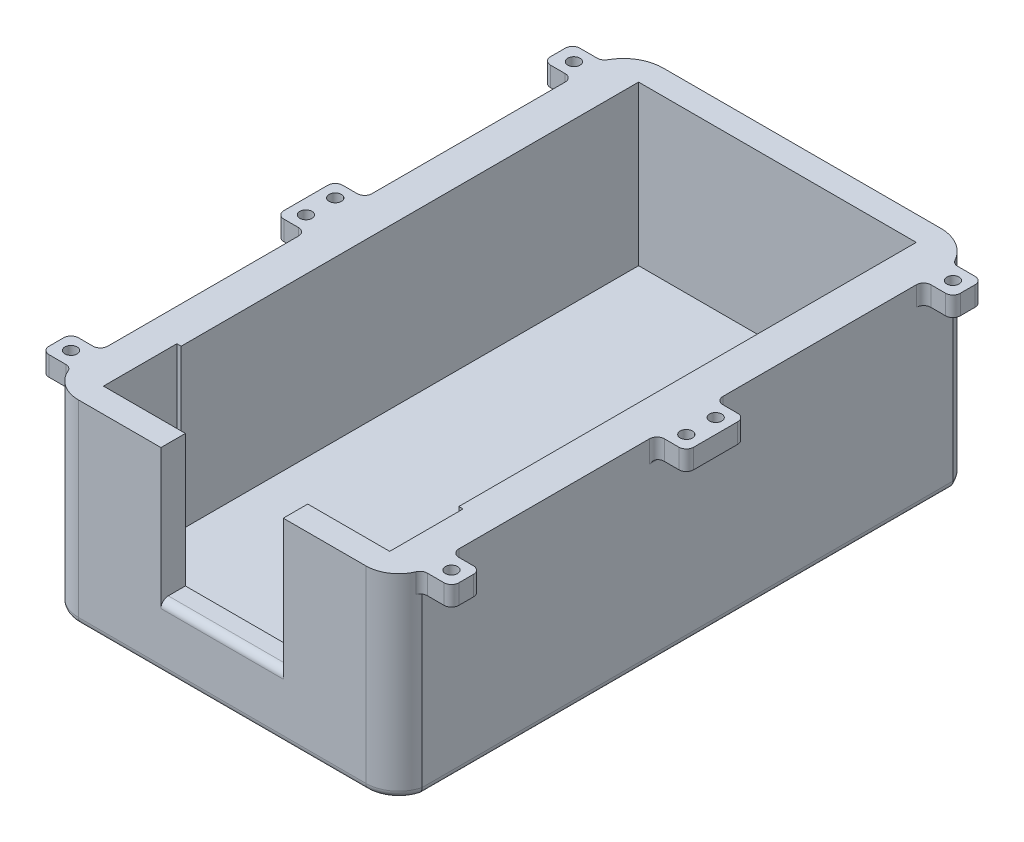
SolidWorks part; units mm, degrees
ref_plane "Front Plane" through (0, 0, 0) normal (0, 0, 1) x (1, 0, 0)
ref_plane "Top Plane" through (0, 0, 0) normal (0, 1, 0) x (1, 0, 0)
ref_plane "Right Plane" through (0, 0, 0) normal (1, 0, 0) x (0, 0, -1)
sketch "Sketch2" plane through (0, 0, 0) normal (0, 1, 0) x (1, 0, 0)
  line L0 (0, 0) -> (0, 286.8389) construction
  line L1 (0, 0) -> (357.4754, 0) construction
  line L2 (0, 0) -> (117, 0)
  line L3 (0, 0) -> (0, 30)
  line L4 (0, 30) -> (1.75, 30)
  line L5 (1.75, 30) -> (1.75, 217)
  line L6 (1.75, 217) -> (115.25, 217)
  line L7 (115.25, 217) -> (115.25, 30)
  line L8 (115.25, 30) -> (117, 30)
  line L9 (117, 30) -> (117, 0)
  line L10 (1.75, 227) -> (115.25, 227)
  line L11 (-13.25, 217) -> (-13.25, 0)
  line L12 (130.25, 217) -> (130.25, 0)
  line L13 (-13.25, 0) -> (0, 0)
  line L14 (1.75, 227) -> (1.75, 217) construction
  line L15 (-0.2607, -10) -> (117.2607, -10)
  arc A0 (1.75, 227) -> (-13.25, 217) centre (1.75, 210.75) ccw
  arc A1 (115.25, 227) -> (130.25, 217) centre (115.25, 210.75) cw
  arc A2 (117.2607, -10) -> (130.25, 0) centre (117.2607, 3.4361) ccw
  arc A3 (-0.2607, -10) -> (-13.25, 0) centre (-0.2607, 3.4361) cw
  dimension "D11" = 10
  dimension "D12" = 217
  dimension "D14" = 113.5
  dimension "D15" = 13.4361
  dimension "D16" = 13.4361
  dimension "D1" = 117
  dimension "D2" = 113.5
  dimension "D3" = 1.75
  dimension "D4" = 1.75
  dimension "D5" = 217
  dimension "D6" = 30
  dimension "D7" = 30
  dimension "D8" = 15
  dimension "D9" = 15
  dimension "D10" = 10
  dimension "D13" = 217
extrude "Boss-Extrude1" add sketch "Sketch2" along normal blind 65 contours A3 L15 A2 L12 A1 L10 A0 L11 L3 L4 L5 L6 L7 L8 L9 L2 region at (-10.4794, 0, -108.5)
sketch "Sketch3" plane through (0, 0, 0) normal (0, -1, 0) x (1, 0, 0)
  line L0 (1.75, -227) -> (115.25, -227) construction
  line L1 (130.25, -217) -> (130.25, 0) construction
  line L2 (-0.2607, 10) -> (117.2607, 10) construction
  line L3 (-13.25, -217) -> (-13.25, 0) construction
  line L4 (1.75, -227) -> (115.25, -227)
  line L5 (130.25, -217) -> (130.25, 0)
  line L6 (-0.2607, 10) -> (117.2607, 10)
  line L7 (-13.25, -217) -> (-13.25, 0)
  arc A0 (-13.25, -217) -> (1.75, -227) centre (1.75, -210.75) ccw construction
  arc A1 (115.25, -227) -> (130.25, -217) centre (115.25, -210.75) ccw construction
  arc A2 (130.25, 0) -> (117.2607, 10) centre (117.2607, -3.4361) ccw construction
  arc A3 (-0.2607, 10) -> (-13.25, 0) centre (-0.2607, -3.4361) ccw construction
  arc A4 (-13.25, -217) -> (1.75, -227) centre (1.75, -210.75) ccw
  arc A5 (115.25, -227) -> (130.25, -217) centre (115.25, -210.75) ccw
  arc A6 (130.25, 0) -> (117.2607, 10) centre (117.2607, -3.4361) ccw
  arc A7 (-0.2607, 10) -> (-13.25, 0) centre (-0.2607, -3.4361) ccw
extrude "Boss-Extrude2" add sketch "Sketch3" along normal blind 15
sketch "Sketch4" plane through (0, 0, 10) normal (0, 0, 1) x (1, 0, 0)
  line L0 (0, 0) -> (117, 0) construction
  line L1 (0, 65) -> (0, 0) construction
  line L2 (117, 65) -> (117, 0) construction
  line L3 (0, 0) -> (117, 0)
  line L4 (0, 65) -> (0, 0)
  line L5 (117, 65) -> (117, 0)
  line L6 (33.5, 65) -> (33.5, 11)
  line L7 (-0.2607, 65) -> (117.2607, 65) construction
  line L8 (33.5, 11) -> (83.5, 11)
  line L9 (83.5, 11) -> (83.5, 65)
  line L11 (33.5, 65) -> (83.5, 65)
  line M10 (117.2607, 65) -> (-0.2607, 65)
  dimension "D1" = 33.5
  dimension "D2" = 33.5
  dimension "D3" = 11
extrude "Cut-Extrude1" cut sketch "Sketch4" against normal blind 10 contours L8 L9 L6 M10 region at (58.5, 38, 10)
sketch "Sketch5" plane through (0, 65, 0) normal (0, 1, 0) x (1, 0, 0)
  line L0 (-13.25, 0) -> (-25.25, 0)
  line L1 (-25.25, 0) -> (-25.25, 12)
  line L2 (-25.25, 12) -> (-13.25, 12)
  line L3 (-13.25, 217) -> (-13.25, 0) construction
  line L4 (130.25, 0) -> (142.25, 0)
  line L5 (142.25, 0) -> (142.25, 12)
  line L6 (142.25, 12) -> (130.25, 12)
  line L7 (130.25, 217) -> (130.25, 0) construction
  line L8 (130.25, 217) -> (142.25, 217)
  line L9 (142.25, 217) -> (142.25, 205)
  line L10 (142.25, 205) -> (130.25, 205)
  line L11 (-13.25, 217) -> (-25.25, 217)
  line L12 (-25.25, 217) -> (-25.25, 205)
  line L13 (-25.25, 205) -> (-13.25, 205)
  line L14 (130.25, 12) -> (130.25, 0)
  line L15 (-13.25, 12) -> (-13.25, 0)
  line L16 (-13.25, 217) -> (-13.25, 205)
  line L17 (130.25, 217) -> (130.25, 205)
  dimension "D1" = 12
  dimension "D2" = 12
  dimension "D3" = 12
  dimension "D4" = 12
  dimension "D5" = 12
  dimension "D6" = 12
  dimension "D7" = 12
  dimension "D8" = 12
extrude "Boss-Extrude3" add sketch "Sketch5" against normal blind 8
sketch "Sketch6" plane through (0, 65, 0) normal (0, 1, 0) x (1, 0, 0)
  line L0 (130.25, 96) -> (142.25, 96)
  line L1 (130.25, 205) -> (130.25, 12) construction
  line L2 (142.25, 96) -> (142.25, 120)
  line L3 (142.25, 120) -> (130.25, 120)
  line L4 (130.25, 120) -> (130.25, 96)
  line L5 (142.25, 108) -> (130.25, 108)
  line L6 (58.5, 217) -> (58.5, 0) construction
  line L7 (-13.25, 96) -> (-25.25, 96)
  line L8 (0, 30) -> (0, 0)
  line L9 (0, 0) -> (117, 0)
  line L10 (117, 0) -> (117, 30)
  line L11 (117, 30) -> (115.25, 30)
  line L12 (115.25, 30) -> (115.25, 217)
  line L13 (115.25, 217) -> (1.75, 217)
  line L14 (1.75, 217) -> (1.75, 30)
  line L15 (1.75, 30) -> (0, 30)
  line L16 (0, 30) -> (0, 0)
  line L17 (0, 0) -> (117, 0)
  line L18 (117, 0) -> (117, 30)
  line L19 (117, 30) -> (115.25, 30)
  line L20 (115.25, 30) -> (115.25, 217)
  line L21 (115.25, 217) -> (1.75, 217)
  line L22 (1.75, 217) -> (1.75, 30)
  line L23 (1.75, 30) -> (0, 30)
  line L24 (-25.25, 96) -> (-25.25, 120)
  line L25 (-25.25, 120) -> (-13.25, 120)
  line L26 (-13.25, 120) -> (-13.25, 96)
  line L27 (-25.25, 108) -> (-13.25, 108)
  line M31 (130.25, 12) -> (130.25, 205)
  line M41 (-13.25, 205) -> (-13.25, 12)
  dimension "D2" = 24
  dimension "D3" = 12
  dimension "D4" = 108
  dimension "D1" = 0
extrude "Boss-Extrude4" add sketch "Sketch6" against normal blind 8 contours L2 L5 L0 M31 | L5 L2 L3 L4 | L27 L24 L7 L26 | L24 L27 L25 M41 region at (136.25, 65, -102) region at (136.25, 65, -114) region at (-19.25, 65, -102) region at (-19.25, 65, -114)
fillet "Fillet1" radius 3 24 edges at (-25.25, 61, -205) (-13.25, 61, -205) (-25.25, 61, -217) (-13.25, 61, -217) (-25.25, 61, -96) (-13.25, 61, -96) (-25.25, 61, -120) (-13.25, 61, -120) (-25.25, 61, -12) (-13.25, 61, -12) (-25.25, 61, 0) (-13.25, 61, 0) (130.25, 61, 0) (142.25, 61, 0) (142.25, 61, -12) (130.25, 61, -12) (130.25, 61, -96) (142.25, 61, -96) (142.25, 61, -120) (130.25, 61, -120) (130.25, 61, -205) (142.25, 61, -205) (142.25, 61, -217) (130.25, 61, -217)
fillet "Fillet2" radius 3 1 edges at (58.5, 11, 10)
sketch "Sketch7" plane through (0, 65, 0) normal (0, 1, 0) x (1, 0, 0)
  line L36 (-25.25, 214) -> (-25.25, 208)
  line L37 (-22.25, 205) -> (-16.25, 205)
  line L38 (-13.25, 202) -> (-13.25, 123)
  line L39 (-16.25, 120) -> (-22.25, 120)
  line L40 (-25.25, 117) -> (-25.25, 99)
  line L41 (-22.25, 96) -> (-16.25, 96)
  line L42 (-13.25, 93) -> (-13.25, 15)
  line L43 (-16.25, 12) -> (-22.25, 12)
  line L44 (-25.25, 9) -> (-25.25, 3)
  line L45 (-22.25, 0) -> (-15.3842, 0)
  line L46 (-0.2607, -10) -> (33.5, -10)
  line L47 (33.5, -10) -> (33.5, 0)
  line L48 (33.5, 0) -> (0, 0)
  line L49 (0, 0) -> (0, 30)
  line L50 (0, 30) -> (1.75, 30)
  line L51 (1.75, 30) -> (1.75, 217)
  line L52 (1.75, 217) -> (115.25, 217)
  line L53 (115.25, 217) -> (115.25, 30)
  line L54 (115.25, 30) -> (117, 30)
  line L55 (117, 30) -> (117, 0)
  line L56 (117, 0) -> (83.5, 0)
  line L57 (83.5, 0) -> (83.5, -10)
  line L58 (83.5, -10) -> (117.2607, -10)
  line L59 (132.3842, 0) -> (139.25, 0)
  line L60 (142.25, 3) -> (142.25, 9)
  line L61 (139.25, 12) -> (133.25, 12)
  line L62 (130.25, 15) -> (130.25, 93)
  line L63 (133.25, 96) -> (139.25, 96)
  line L64 (142.25, 99) -> (142.25, 117)
  line L65 (139.25, 120) -> (133.25, 120)
  line L66 (130.25, 123) -> (130.25, 202)
  line L67 (133.25, 205) -> (139.25, 205)
  line L68 (142.25, 208) -> (142.25, 214)
  line L69 (139.25, 217) -> (132.1319, 217)
  line L70 (115.25, 227) -> (1.75, 227)
  line L71 (-15.1319, 217) -> (-22.25, 217)
  line L72 (-25.25, 214) -> (-25.25, 208)
  line L73 (-22.25, 205) -> (-16.25, 205)
  line L74 (-13.25, 202) -> (-13.25, 123)
  line L75 (-16.25, 120) -> (-22.25, 120)
  line L76 (-25.25, 117) -> (-25.25, 99)
  line L77 (-22.25, 96) -> (-16.25, 96)
  line L78 (-13.25, 93) -> (-13.25, 15)
  line L79 (-16.25, 12) -> (-22.25, 12)
  line L80 (-25.25, 9) -> (-25.25, 3)
  line L81 (-22.25, 0) -> (-15.3842, 0)
  line L88 (1.75, 217) -> (115.25, 217)
  line L89 (115.25, 217) -> (115.25, 30)
  line L90 (115.25, 30) -> (117, 30)
  line L91 (117, 30) -> (117, 0)
  line L92 (117, 0) -> (83.5, 0)
  line L93 (83.5, 0) -> (83.5, -10)
  line L94 (83.5, -10) -> (117.2607, -10)
  line L95 (132.3842, 0) -> (139.25, 0)
  line L96 (142.25, 3) -> (142.25, 9)
  line L97 (139.25, 12) -> (133.25, 12)
  line L98 (130.25, 15) -> (130.25, 93)
  line L99 (133.25, 96) -> (139.25, 96)
  line L100 (142.25, 99) -> (142.25, 117)
  line L101 (139.25, 120) -> (133.25, 120)
  line L102 (130.25, 123) -> (130.25, 202)
  line L103 (133.25, 205) -> (139.25, 205)
  line L104 (142.25, 208) -> (142.25, 214)
  line L105 (139.25, 217) -> (132.1319, 217)
  line L106 (115.25, 227) -> (1.75, 227)
  line L107 (-15.1319, 217) -> (-22.25, 217)
  circle A0 centre (136.25, 114) radius 2.5
  circle A1 centre (136.25, 102) radius 2.5
  circle A2 centre (136.25, 211) radius 2.5
  circle A3 centre (-18.691, 211) radius 2.5
  circle A4 centre (-19.25, 114) radius 2.5
  circle A5 centre (-19.25, 102) radius 2.5
  circle A6 centre (-19.25, 6) radius 2.5
  circle A7 centre (136.25, 6) radius 2.5
  arc A28 (-25.25, 208) -> (-22.25, 205) centre (-22.25, 208) ccw
  arc A29 (-13.25, 202) -> (-16.25, 205) centre (-16.25, 202) ccw
  arc A30 (-16.25, 120) -> (-13.25, 123) centre (-16.25, 123) ccw
  arc A31 (-22.25, 120) -> (-25.25, 117) centre (-22.25, 117) ccw
  arc A32 (-25.25, 99) -> (-22.25, 96) centre (-22.25, 99) ccw
  arc A33 (-13.25, 93) -> (-16.25, 96) centre (-16.25, 93) ccw
  arc A34 (-16.25, 12) -> (-13.25, 15) centre (-16.25, 15) ccw
  arc A35 (-22.25, 12) -> (-25.25, 9) centre (-22.25, 9) ccw
  arc A36 (-25.25, 3) -> (-22.25, 0) centre (-22.25, 3) ccw
  arc A37 (-12.6238, -1.8252) -> (-15.3842, 0) centre (-15.3842, -3) ccw
  arc A38 (-12.6238, -1.8252) -> (-0.2607, -10) centre (-0.2607, 3.4361) ccw
  arc A39 (117.2607, -10) -> (129.6238, -1.8252) centre (117.2607, 3.4361) ccw
  arc A40 (132.3842, 0) -> (129.6238, -1.8252) centre (132.3842, -3) ccw
  arc A41 (139.25, 0) -> (142.25, 3) centre (139.25, 3) ccw
  arc A42 (142.25, 9) -> (139.25, 12) centre (139.25, 9) ccw
  arc A43 (130.25, 15) -> (133.25, 12) centre (133.25, 15) ccw
  arc A44 (133.25, 96) -> (130.25, 93) centre (133.25, 93) ccw
  arc A45 (139.25, 96) -> (142.25, 99) centre (139.25, 99) ccw
  arc A46 (142.25, 117) -> (139.25, 120) centre (139.25, 117) ccw
  arc A47 (130.25, 123) -> (133.25, 120) centre (133.25, 123) ccw
  arc A48 (133.25, 205) -> (130.25, 202) centre (133.25, 202) ccw
  arc A49 (139.25, 205) -> (142.25, 208) centre (139.25, 208) ccw
  arc A50 (142.25, 214) -> (139.25, 217) centre (139.25, 214) ccw
  arc A51 (129.501, 218.5584) -> (132.1319, 217) centre (132.1319, 220) ccw
  arc A52 (129.501, 218.5584) -> (115.25, 227) centre (115.25, 210.75) ccw
  arc A53 (1.75, 227) -> (-12.501, 218.5584) centre (1.75, 210.75) ccw
  arc A54 (-15.1319, 217) -> (-12.501, 218.5584) centre (-15.1319, 220) ccw
  arc A55 (-22.25, 217) -> (-25.25, 214) centre (-22.25, 214) ccw
  arc A56 (-25.25, 208) -> (-22.25, 205) centre (-22.25, 208) ccw
  arc A57 (-13.25, 202) -> (-16.25, 205) centre (-16.25, 202) ccw
  arc A58 (-16.25, 120) -> (-13.25, 123) centre (-16.25, 123) ccw
  arc A59 (-22.25, 120) -> (-25.25, 117) centre (-22.25, 117) ccw
  arc A60 (-25.25, 99) -> (-22.25, 96) centre (-22.25, 99) ccw
  arc A61 (-13.25, 93) -> (-16.25, 96) centre (-16.25, 93) ccw
  arc A62 (-16.25, 12) -> (-13.25, 15) centre (-16.25, 15) ccw
  arc A63 (-22.25, 12) -> (-25.25, 9) centre (-22.25, 9) ccw
  arc A64 (-25.25, 3) -> (-22.25, 0) centre (-22.25, 3) ccw
  arc A65 (-12.6238, -1.8252) -> (-15.3842, 0) centre (-15.3842, -3) ccw
  arc A67 (117.2607, -10) -> (129.6238, -1.8252) centre (117.2607, 3.4361) ccw
  arc A68 (132.3842, 0) -> (129.6238, -1.8252) centre (132.3842, -3) ccw
  arc A69 (139.25, 0) -> (142.25, 3) centre (139.25, 3) ccw
  arc A70 (142.25, 9) -> (139.25, 12) centre (139.25, 9) ccw
  arc A71 (130.25, 15) -> (133.25, 12) centre (133.25, 15) ccw
  arc A72 (133.25, 96) -> (130.25, 93) centre (133.25, 93) ccw
  arc A73 (139.25, 96) -> (142.25, 99) centre (139.25, 99) ccw
  arc A74 (142.25, 117) -> (139.25, 120) centre (139.25, 117) ccw
  arc A75 (130.25, 123) -> (133.25, 120) centre (133.25, 123) ccw
  arc A76 (133.25, 205) -> (130.25, 202) centre (133.25, 202) ccw
  arc A77 (139.25, 205) -> (142.25, 208) centre (139.25, 208) ccw
  arc A78 (142.25, 214) -> (139.25, 217) centre (139.25, 214) ccw
  arc A79 (129.501, 218.5584) -> (132.1319, 217) centre (132.1319, 220) ccw
  arc A80 (129.501, 218.5584) -> (115.25, 227) centre (115.25, 210.75) ccw
  arc A81 (1.75, 227) -> (-12.501, 218.5584) centre (1.75, 210.75) ccw
  arc A82 (-15.1319, 217) -> (-12.501, 218.5584) centre (-15.1319, 220) ccw
  arc A83 (-22.25, 217) -> (-25.25, 214) centre (-22.25, 214) ccw
  dimension "D2" = 5
  dimension "D3" = 5
  dimension "D4" = 5
  dimension "D5" = 5
  dimension "D6" = 5
  dimension "D7" = 5
  dimension "D8" = 5
  dimension "D9" = 5
  dimension "D10" = 6
  dimension "D11" = 6
  dimension "D12" = 6
  dimension "D13" = 6
  dimension "D14" = 6
  dimension "D15" = 6
  dimension "D16" = 6
  dimension "D17" = 6
  dimension "D18" = 6
  dimension "D19" = 6
  dimension "D20" = 6
  dimension "D21" = 6
  dimension "D22" = 6
  dimension "D23" = 6
  dimension "D24" = 6
  dimension "D1" = 0
extrude "Cut-Extrude2" cut sketch "Sketch7" against normal blind 6 contours A6 | A5 | A4 | A3 | A2 | A7 | A0 | A1 region at (136.25, 65, -211) region at (-18.691, 65, -211) region at (-19.25, 65, -114) region at (-19.25, 65, -102) region at (-19.25, 65, -6) region at (136.25, 65, -6)
fillet "Fillet3" radius 3 8 edges at (-8.457, -15, 7.2104) (124.2639, -15, -224.2708) (-7.2639, -15, -224.2708) (58.5, -15, -227) (58.5, -15, 10) (125.457, -15, 7.2104) (130.25, -15, -108.5) (-13.25, -15, -108.5)
fillet "Fillet6" radius 1 2 edges at (130.25, 57, -108) (-13.25, 57, -108)
sketch "Sketch10" plane through (0, 65, 0) normal (0, 1, 0) x (1, 0, 0)
  line L36 (-25.25, 214) -> (-25.25, 208)
  line L37 (-22.25, 205) -> (-16.25, 205)
  line L38 (-13.25, 202) -> (-13.25, 123)
  line L39 (-16.25, 120) -> (-22.25, 120)
  line L40 (-25.25, 117) -> (-25.25, 99)
  line L41 (-22.25, 96) -> (-16.25, 96)
  line L42 (-13.25, 93) -> (-13.25, 15)
  line L43 (-16.25, 12) -> (-22.25, 12)
  line L44 (-25.25, 9) -> (-25.25, 3)
  line L45 (-22.25, 0) -> (-15.3842, 0)
  line L46 (-0.2607, -10) -> (33.5, -10)
  line L47 (33.5, -10) -> (33.5, 0)
  line L48 (33.5, 0) -> (0, 0)
  line L49 (0, 0) -> (0, 30)
  line L50 (0, 30) -> (1.75, 30)
  line L51 (1.75, 30) -> (1.75, 217)
  line L52 (1.75, 217) -> (115.25, 217)
  line L53 (115.25, 217) -> (115.25, 30)
  line L54 (115.25, 30) -> (117, 30)
  line L55 (117, 30) -> (117, 0)
  line L56 (117, 0) -> (83.5, 0)
  line L57 (83.5, 0) -> (83.5, -10)
  line L58 (83.5, -10) -> (117.2607, -10)
  line L59 (132.3842, 0) -> (139.25, 0)
  line L60 (142.25, 3) -> (142.25, 9)
  line L61 (139.25, 12) -> (133.25, 12)
  line L62 (130.25, 15) -> (130.25, 93)
  line L63 (133.25, 96) -> (139.25, 96)
  line L64 (142.25, 99) -> (142.25, 117)
  line L65 (139.25, 120) -> (133.25, 120)
  line L66 (130.25, 123) -> (130.25, 202)
  line L67 (133.25, 205) -> (139.25, 205)
  line L68 (142.25, 208) -> (142.25, 214)
  line L69 (139.25, 217) -> (132.1319, 217)
  line L70 (115.25, 227) -> (1.75, 227)
  line L71 (-15.1319, 217) -> (-22.25, 217)
  line L72 (-25.25, 214) -> (-25.25, 208)
  line L73 (-22.25, 205) -> (-16.25, 205)
  line L74 (-13.25, 202) -> (-13.25, 123)
  line L75 (-16.25, 120) -> (-22.25, 120)
  line L76 (-25.25, 117) -> (-25.25, 99)
  line L77 (-22.25, 96) -> (-16.25, 96)
  line L78 (-13.25, 93) -> (-13.25, 15)
  line L79 (-16.25, 12) -> (-22.25, 12)
  line L80 (-25.25, 9) -> (-25.25, 3)
  line L81 (-22.25, 0) -> (-15.3842, 0)
  line L82 (-0.2607, -10) -> (33.5, -10)
  line L83 (33.5, -10) -> (33.5, 0)
  line L84 (33.5, 0) -> (0, 0)
  line L85 (0, 0) -> (0, 30)
  line L86 (0, 30) -> (1.75, 30)
  line L87 (1.75, 30) -> (1.75, 217)
  line L88 (1.75, 217) -> (115.25, 217)
  line L89 (115.25, 217) -> (115.25, 30)
  line L90 (115.25, 30) -> (117, 30)
  line L91 (117, 30) -> (117, 0)
  line L92 (117, 0) -> (83.5, 0)
  line L93 (83.5, 0) -> (83.5, -10)
  line L94 (83.5, -10) -> (117.2607, -10)
  line L95 (132.3842, 0) -> (139.25, 0)
  line L96 (142.25, 3) -> (142.25, 9)
  line L97 (139.25, 12) -> (133.25, 12)
  line L98 (130.25, 15) -> (130.25, 93)
  line L99 (133.25, 96) -> (139.25, 96)
  line L100 (142.25, 99) -> (142.25, 117)
  line L101 (139.25, 120) -> (133.25, 120)
  line L102 (130.25, 123) -> (130.25, 202)
  line L103 (133.25, 205) -> (139.25, 205)
  line L104 (142.25, 208) -> (142.25, 214)
  line L105 (139.25, 217) -> (132.1319, 217)
  line L106 (115.25, 227) -> (1.75, 227)
  line L107 (-15.1319, 217) -> (-22.25, 217)
  arc A28 (-25.25, 208) -> (-22.25, 205) centre (-22.25, 208) ccw
  arc A29 (-13.25, 202) -> (-16.25, 205) centre (-16.25, 202) ccw
  arc A30 (-16.25, 120) -> (-13.25, 123) centre (-16.25, 123) ccw
  arc A31 (-22.25, 120) -> (-25.25, 117) centre (-22.25, 117) ccw
  arc A32 (-25.25, 99) -> (-22.25, 96) centre (-22.25, 99) ccw
  arc A33 (-13.25, 93) -> (-16.25, 96) centre (-16.25, 93) ccw
  arc A34 (-16.25, 12) -> (-13.25, 15) centre (-16.25, 15) ccw
  arc A35 (-22.25, 12) -> (-25.25, 9) centre (-22.25, 9) ccw
  arc A36 (-25.25, 3) -> (-22.25, 0) centre (-22.25, 3) ccw
  arc A37 (-12.6238, -1.8252) -> (-15.3842, 0) centre (-15.3842, -3) ccw
  arc A38 (-12.6238, -1.8252) -> (-0.2607, -10) centre (-0.2607, 3.4361) ccw
  arc A39 (117.2607, -10) -> (129.6238, -1.8252) centre (117.2607, 3.4361) ccw
  arc A40 (132.3842, 0) -> (129.6238, -1.8252) centre (132.3842, -3) ccw
  arc A41 (139.25, 0) -> (142.25, 3) centre (139.25, 3) ccw
  arc A42 (142.25, 9) -> (139.25, 12) centre (139.25, 9) ccw
  arc A43 (130.25, 15) -> (133.25, 12) centre (133.25, 15) ccw
  arc A44 (133.25, 96) -> (130.25, 93) centre (133.25, 93) ccw
  arc A45 (139.25, 96) -> (142.25, 99) centre (139.25, 99) ccw
  arc A46 (142.25, 117) -> (139.25, 120) centre (139.25, 117) ccw
  arc A47 (130.25, 123) -> (133.25, 120) centre (133.25, 123) ccw
  arc A48 (133.25, 205) -> (130.25, 202) centre (133.25, 202) ccw
  arc A49 (139.25, 205) -> (142.25, 208) centre (139.25, 208) ccw
  arc A50 (142.25, 214) -> (139.25, 217) centre (139.25, 214) ccw
  arc A51 (129.501, 218.5584) -> (132.1319, 217) centre (132.1319, 220) ccw
  arc A52 (129.501, 218.5584) -> (115.25, 227) centre (115.25, 210.75) ccw
  arc A53 (1.75, 227) -> (-12.501, 218.5584) centre (1.75, 210.75) ccw
  arc A54 (-15.1319, 217) -> (-12.501, 218.5584) centre (-15.1319, 220) ccw
  arc A55 (-22.25, 217) -> (-25.25, 214) centre (-22.25, 214) ccw
  arc A56 (-25.25, 208) -> (-22.25, 205) centre (-22.25, 208) ccw
  arc A57 (-13.25, 202) -> (-16.25, 205) centre (-16.25, 202) ccw
  arc A58 (-16.25, 120) -> (-13.25, 123) centre (-16.25, 123) ccw
  arc A59 (-22.25, 120) -> (-25.25, 117) centre (-22.25, 117) ccw
  arc A60 (-25.25, 99) -> (-22.25, 96) centre (-22.25, 99) ccw
  arc A61 (-13.25, 93) -> (-16.25, 96) centre (-16.25, 93) ccw
  arc A62 (-16.25, 12) -> (-13.25, 15) centre (-16.25, 15) ccw
  arc A63 (-22.25, 12) -> (-25.25, 9) centre (-22.25, 9) ccw
  arc A64 (-25.25, 3) -> (-22.25, 0) centre (-22.25, 3) ccw
  arc A65 (-12.6238, -1.8252) -> (-15.3842, 0) centre (-15.3842, -3) ccw
  arc A66 (-12.6238, -1.8252) -> (-0.2607, -10) centre (-0.2607, 3.4361) ccw
  arc A67 (117.2607, -10) -> (129.6238, -1.8252) centre (117.2607, 3.4361) ccw
  arc A68 (132.3842, 0) -> (129.6238, -1.8252) centre (132.3842, -3) ccw
  arc A69 (139.25, 0) -> (142.25, 3) centre (139.25, 3) ccw
  arc A70 (142.25, 9) -> (139.25, 12) centre (139.25, 9) ccw
  arc A71 (130.25, 15) -> (133.25, 12) centre (133.25, 15) ccw
  arc A72 (133.25, 96) -> (130.25, 93) centre (133.25, 93) ccw
  arc A73 (139.25, 96) -> (142.25, 99) centre (139.25, 99) ccw
  arc A74 (142.25, 117) -> (139.25, 120) centre (139.25, 117) ccw
  arc A75 (130.25, 123) -> (133.25, 120) centre (133.25, 123) ccw
  arc A76 (133.25, 205) -> (130.25, 202) centre (133.25, 202) ccw
  arc A77 (139.25, 205) -> (142.25, 208) centre (139.25, 208) ccw
  arc A78 (142.25, 214) -> (139.25, 217) centre (139.25, 214) ccw
  arc A79 (129.501, 218.5584) -> (132.1319, 217) centre (132.1319, 220) ccw
  arc A80 (129.501, 218.5584) -> (115.25, 227) centre (115.25, 210.75) ccw
  arc A81 (1.75, 227) -> (-12.501, 218.5584) centre (1.75, 210.75) ccw
  arc A82 (-15.1319, 217) -> (-12.501, 218.5584) centre (-15.1319, 220) ccw
  arc A83 (-22.25, 217) -> (-25.25, 214) centre (-22.25, 214) ccw
  dimension "D1" = 0
